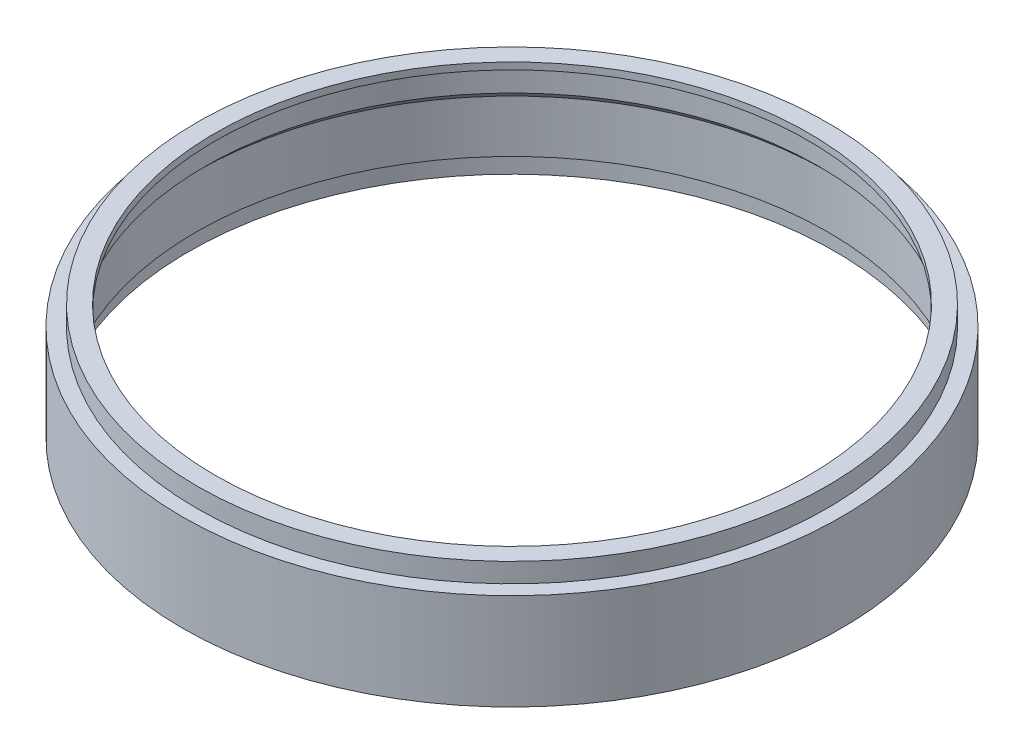
SolidWorks part; units mm, degrees
ref_plane "Front Plane" through (0, 0, 0) normal (0, 0, 1) x (1, 0, 0)
ref_plane "Top Plane" through (0, 0, 0) normal (0, 1, 0) x (1, 0, 0)
ref_plane "Right Plane" through (0, 0, 0) normal (1, 0, 0) x (0, 0, -1)
ref_axis "Axis1" through (0, 0, 0) along (0, 1, 0)
sketch "Sketch1" plane through (0, 0, 0) normal (0, 0, 1) x (1, 0, 0)
  line L0 (0, 0) -> (0, -50000) construction
  line L1 (-48.35, 0) -> (-48.35, 14.15)
  line L2 (-48.35, 0) -> (-47.4, 0)
  line L3 (-47.4, 0) -> (-47.4, 3)
  line L4 (-47.4, 3) -> (-46.35, 3)
  line L5 (-46.35, 3) -> (-46.35, 10.67)
  line L7 (-48.35, 0) -> (-48.35, -9.6235) construction
  line L8 (-46.35, 10.67) -> (-45.02, 12)
  line L10 (-45.02, 12) -> (-45.02, 16)
  line L11 (-45.02, 16) -> (-43.52, 16)
  line L12 (-47.35, 3) -> (-47.35, 0) construction
  line L13 (-46.35, 3) -> (-46.35, -7.15) construction
  line L14 (-45, 16.65) -> (-45, 12.65) construction
  line L17 (-43.52, 16) -> (-43.52, 17)
  line L26 (-46.22, 17) -> (-46.22, 14.15)
  line L27 (-46.22, 14.15) -> (-48.35, 14.15)
  line L31 (46.35, 3) -> (-46.35, 3) construction
  line L32 (-46.22, 17) -> (-43.52, 17)
  line L34 (-48.35, 15.15) -> (48.35, 15.15) construction
  point P12 (-45, 12.2383)
  point P14 (-45, 12)
  point P22 (-45.02, 12.65)
  point P23 (-43.52, 17.5183)
  point P31 (-45, 12)
  dimension "D1" = 135
  dimension "D2" = 0.02
  dimension "D3" = 1.2
  dimension "D4" = 1.5
  dimension "D5" = 1
  dimension "D6" = 0.05
  dimension "D7" = 4
  dimension "D8" = 1
revolve "Revolve1" add sketch "Sketch1" angle 360 about L0
